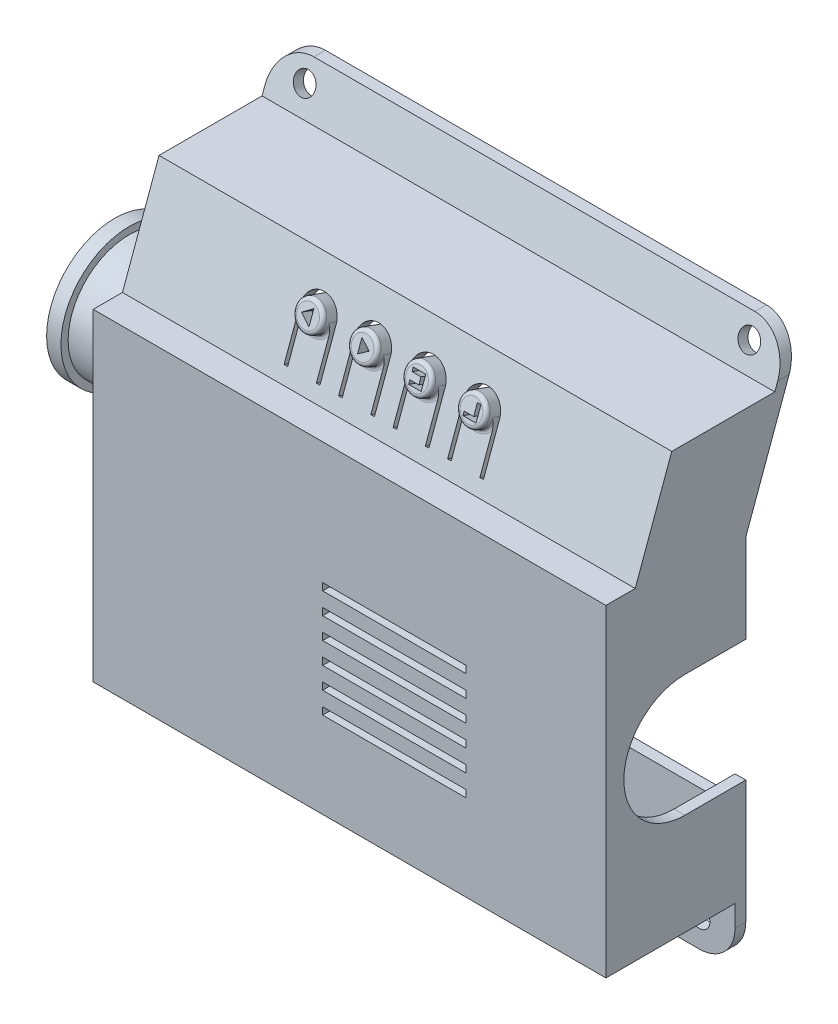
SolidWorks part; units mm, degrees
ref_plane "前视基准面" through (0, 0, 0) normal (0, 0, 1) x (1, 0, 0)
ref_plane "上视基准面" through (0, 0, 0) normal (0, 1, 0) x (1, 0, 0)
ref_plane "右视基准面" through (0, 0, 0) normal (1, 0, 0) x (0, 0, -1)
sketch "草图1" plane through (0, 0, 0) normal (0, 0, 1) x (1, 0, 0)
  line L1 (0, 0) -> (70, 0)
  line L2 (0, 0) -> (0, 42)
  line L3 (0, 42) -> (70, 42)
  line L4 (70, 0) -> (70, 42)
  dimension "D1" = 70
  dimension "D2" = 42
extrude "凸台-拉伸1" add sketch "草图1" along normal blind 1.5
sketch "草图2" plane through (0, 0, 0) normal (0, -1, 0) x (1, 0, 0)
  line L0 (70, 1.5) -> (70, 0) construction
  line L1 (0, 1.5) -> (70, 1.5)
  line L2 (0, 1.5) -> (0, -16.5)
  line L3 (0, -16.5) -> (70, -16.5)
  line L4 (70, 1.5) -> (70, -16.5)
  dimension "D1" = 18
extrude "凸台-拉伸2" add sketch "草图2" along normal blind 1.5
sketch "草图3" plane through (0, 0, -16.5) normal (0, 0, -1) x (-1, 0, 0)
  line L1 (-70, 10) -> (0, 10)
  line L2 (-70, 10) -> (-70, -9.5)
  line L3 (-70, -9.5) -> (0, -9.5)
  line L4 (0, 10) -> (0, -9.5)
  line L5 (0, -1.5) -> (-70, -1.5) construction
  line L7 (0, 0) -> (-70, 0) construction
  dimension "D1" = 8
  dimension "D2" = 10
extrude "凸台-拉伸3" add sketch "草图3" along normal blind 1.5
sketch "草图5" plane through (70, 0, 0) normal (1, 0, 0) x (0, 0, -1)
  line L0 (18, 10) -> (18, -9.5) construction
  line L1 (-1.5, 42) -> (18, 42)
  line L2 (-1.5, 42) -> (-1.5, -1.5)
  line L3 (-1.5, -1.5) -> (18, -1.5)
  line L4 (18, 42) -> (18, -1.5)
  line L5 (16.5, -1.5) -> (-1.5, -1.5) construction
extrude "凸台-拉伸4" add sketch "草图5" against normal blind 1.5
sketch "草图6" plane through (0, 0, 0) normal (-1, 0, 0) x (0, 0, 1)
  line L0 (-18, -9.5) -> (-18, 10) construction
  line L1 (1.5, 42) -> (-18, 42)
  line L2 (1.5, 42) -> (1.5, -1.5)
  line L3 (1.5, -1.5) -> (-18, -1.5)
  line L4 (-18, 42) -> (-18, -1.5)
  line L5 (1.5, -1.5) -> (-16.5, -1.5) construction
extrude "凸台-拉伸5" add sketch "草图6" along normal blind 1.5
sketch "草图7" plane through (-1.5, 0, 0) normal (-1, 0, 0) x (0, 0, 1)
  line L0 (-8, 21.5) -> (-8, 13.5) construction
  line L5 (-5, 21.5) -> (-5, 13.5)
  line L6 (-11, 21.5) -> (-11, 13.5)
  line L7 (-18, 42) -> (-18, -1.5) construction
  line L8 (-18, -1.5) -> (1.5, -1.5) construction
  arc A0 (-5, 21.5) -> (-11, 21.5) centre (-8, 21.5) ccw
  arc A1 (-11, 13.5) -> (-5, 13.5) centre (-8, 13.5) ccw
  point P2 (-8, 17.5)
  dimension "D3" = 15
  dimension "D1" = 7
  dimension "D2" = 13
  dimension "D4" = 23
extrude "切除-拉伸1" cut sketch "草图7" against normal blind 1.5
sketch "草图8" plane through (-1.5, 0, 0) normal (-1, 0, 0) x (0, 0, 1)
  line L0 (-18, 42) -> (-25.8665, 63.6129)
  line L1 (-25.8665, 63.6129) -> (-24.2702, 63.6129)
  line L2 (-24.2702, 63.6129) -> (-16.4037, 42)
  line L3 (1.5, 42) -> (-18, 42) construction
  line L4 (-18, 42) -> (-16.4037, 42)
  line L5 (-18, 42) -> (-18, -1.5) construction
  dimension "D1" = 23
  dimension "D2" = 160
  dimension "D3" = 1.5
extrude "凸台-拉伸6" add sketch "草图8" against normal blind 71.5
sketch "草图9" plane through (-1.5, 0, 0) normal (-1, 0, 0) x (0, 0, 1)
  line L0 (-3.6336, 42) -> (-8.7639, 56.0954)
  line L1 (1.5, 42) -> (-16.4037, 42) construction
  line L3 (-7.6807, 57.5049) -> (-2.5833, 43.5)
  line L5 (-16.4037, 42) -> (-24.2702, 63.6129) construction
  line L6 (-7.6807, 57.5049) -> (-22.0471, 57.5049)
  line L7 (-22.0471, 57.5049) -> (-21.534, 56.0954)
  line L8 (-21.534, 56.0954) -> (-8.7639, 56.0954)
  line L9 (-2.5833, 43.5) -> (1.5, 43.5)
  line L10 (1.5, 43.5) -> (1.5, 42)
  line L11 (1.5, 42) -> (-3.6336, 42)
  dimension "D1" = 1.5
  dimension "D2" = 12
  dimension "D3" = 1.5
  dimension "D4" = 15
extrude "凸台-拉伸7" add sketch "草图9" against normal blind 71.5
sketch "草图11" plane through (-1.5, 0, 0) normal (-1, 0, 0) x (0, 0, 1)
  line L0 (-21.534, 56.0954) -> (-8.7639, 56.0954)
  line L1 (-8.7639, 56.0954) -> (-3.6336, 42)
  line L2 (-3.6336, 42) -> (-16.4037, 42)
  line L3 (-3.6336, 42) -> (-16.4037, 42) construction
  line L4 (-16.4037, 42) -> (-21.534, 56.0954) construction
  line L5 (-16.4037, 42) -> (-21.534, 56.0954)
extrude "凸台-拉伸10" add sketch "草图11" against normal blind 1.5
sketch "草图12" plane through (70, 0, 0) normal (1, 0, 0) x (0, 0, -1)
  line L0 (8.7639, 56.0954) -> (21.534, 56.0954)
  line L1 (21.534, 56.0954) -> (16.4037, 42)
  line L2 (16.4037, 42) -> (3.6336, 42)
  line L3 (3.6336, 42) -> (8.7639, 56.0954)
extrude "凸台-拉伸11" add sketch "草图12" against normal blind 1.5
sketch "草图13" plane through (0, -0.872, -2.3959) normal (0, -0.342, -0.9397) x (-1, 0, 0)
  line L0 (0, 45.6235) -> (0, 15.5533) construction
  line L1 (-68.5, 44.6235) -> (0, 44.6235)
  line L2 (-68.5, 44.6235) -> (-68.5, 50.6235)
  line L3 (-68.5, 50.6235) -> (0, 50.6235)
  line L4 (0, 44.6235) -> (0, 50.6235)
  line L6 (-68.5, 39.4671) -> (-68.5, 0) construction
  line L7 (-68.5, 45.6235) -> (-70, 45.6235) construction
  dimension "D1" = 6
  dimension "D2" = 5
extrude "切除-拉伸2" cut sketch "草图13" against normal blind 1.5
sketch "草图14" plane through (0, 3.7453, 10.29) normal (0, -0.342, -0.9397) x (-1, 0, 0)
  line L0 (-68.5, 40.7099) -> (0, 40.7099) construction
  line L1 (-54.75, 50.6235) -> (-53.25, 50.6235)
  line L2 (-54.75, 50.6235) -> (-54.75, 55.7099)
  line L3 (-54.75, 55.7099) -> (-53.25, 55.7099)
  line L4 (-53.25, 50.6235) -> (-53.25, 55.7099)
  line L5 (-34.25, 40.7099) -> (-34.25, 65.8956) construction
  line L6 (-15.25, 50.6235) -> (-15.25, 55.7099)
  line L7 (-13.75, 55.7099) -> (-15.25, 55.7099)
  line L8 (-13.75, 50.6235) -> (-13.75, 55.7099)
  line L9 (-13.75, 50.6235) -> (-15.25, 50.6235)
  line L10 (-68.5, 55.7099) -> (0, 55.7099) construction
  line L11 (0, 50.6235) -> (-68.5, 50.6235) construction
  dimension "D1" = 1.5
  dimension "D2" = 38
extrude "凸台-拉伸12" add sketch "草图14" along normal blind 13.5
sketch "草图15" plane through (0, 4.2583, 11.6995) normal (0, 0.342, 0.9397) x (1, 0, 0)
  line L0 (34.25, 56.6639) -> (34.25, 29.0672) construction
  line L1 (70, 56.6639) -> (-1.5, 56.6639) construction
  line L2 (30.45, 51.83) -> (30.45, 31.4798) construction
  line L3 (38.05, 51.83) -> (38.05, 31.4798) construction
  line L4 (45.65, 54.4883) -> (45.65, 27.6418) construction
  line L5 (22.85, 54.4883) -> (22.85, 27.6418) construction
  line L11 (20.35, 43.7602) -> (20.35, 50.3471)
  line L17 (20.85, 43.7602) -> (20.85, 50.3471)
  line L18 (20.85, 43.7602) -> (20.35, 43.7602)
  line L19 (24.85, 43.7602) -> (25.35, 43.7602)
  line L20 (20.85, 41.7602) -> (20.85, 50.3471) construction
  line L21 (20.35, 41.7602) -> (20.35, 50.3471) construction
  line L22 (24.85, 43.7602) -> (24.85, 50.3471)
  line L23 (25.35, 43.7602) -> (25.35, 50.3471)
  line L24 (70, 41.7602) -> (-1.5, 41.7602) construction
  line L31 (26.65, 56.6639) -> (26.65, 29.0672) construction
  line L32 (27.95, 43.7602) -> (27.95, 50.3471)
  line L33 (28.45, 43.7602) -> (28.45, 50.3471)
  line L34 (28.45, 43.7602) -> (27.95, 43.7602)
  line L35 (32.45, 43.7602) -> (32.95, 43.7602)
  line L36 (32.45, 43.7602) -> (32.45, 50.3471)
  line L37 (32.95, 43.7602) -> (32.95, 50.3471)
  line L38 (35.55, 43.7602) -> (35.55, 50.3471)
  line L39 (36.05, 43.7602) -> (36.05, 50.3471)
  line L40 (36.05, 43.7602) -> (35.55, 43.7602)
  line L41 (40.05, 43.7602) -> (40.55, 43.7602)
  line L42 (40.05, 43.7602) -> (40.05, 50.3471)
  line L43 (40.55, 43.7602) -> (40.55, 50.3471)
  line L44 (43.15, 43.7602) -> (43.15, 50.3471)
  line L45 (43.65, 43.7602) -> (43.65, 50.3471)
  line L46 (43.65, 43.7602) -> (43.15, 43.7602)
  line L47 (47.65, 43.7602) -> (48.15, 43.7602)
  line L48 (47.65, 43.7602) -> (47.65, 50.3471)
  line L49 (48.15, 43.7602) -> (48.15, 50.3471)
  arc A0 (22.85, 52.8471) -> (20.35, 50.3471) centre (22.85, 50.3471) ccw
  arc A1 (22.85, 52.3471) -> (20.85, 50.3471) centre (22.85, 50.3471) ccw
  arc A2 (22.85, 52.3471) -> (24.85, 50.3471) centre (22.85, 50.3471) cw
  arc A3 (22.85, 52.8471) -> (25.35, 50.3471) centre (22.85, 50.3471) cw
  arc A8 (30.45, 52.8471) -> (27.95, 50.3471) centre (30.45, 50.3471) ccw
  arc A9 (30.45, 52.3471) -> (28.45, 50.3471) centre (30.45, 50.3471) ccw
  arc A10 (30.45, 52.3471) -> (32.45, 50.3471) centre (30.45, 50.3471) cw
  arc A11 (30.45, 52.8471) -> (32.95, 50.3471) centre (30.45, 50.3471) cw
  arc A12 (38.05, 52.8471) -> (35.55, 50.3471) centre (38.05, 50.3471) ccw
  arc A13 (38.05, 52.3471) -> (36.05, 50.3471) centre (38.05, 50.3471) ccw
  arc A14 (38.05, 52.3471) -> (40.05, 50.3471) centre (38.05, 50.3471) cw
  arc A15 (38.05, 52.8471) -> (40.55, 50.3471) centre (38.05, 50.3471) cw
  arc A16 (45.65, 52.8471) -> (43.15, 50.3471) centre (45.65, 50.3471) ccw
  arc A17 (45.65, 52.3471) -> (43.65, 50.3471) centre (45.65, 50.3471) ccw
  arc A18 (45.65, 52.3471) -> (47.65, 50.3471) centre (45.65, 50.3471) cw
  arc A19 (45.65, 52.8471) -> (48.15, 50.3471) centre (45.65, 50.3471) cw
  dimension "D1" = 7.6
  dimension "D2" = 7.6
  dimension "D4" = 4
  dimension "D5" = 2
  dimension "D3" = 0.5
extrude "切除-拉伸3" cut sketch "草图15" against normal up to next
sketch "草图16" plane through (0, 4.2583, 11.6995) normal (0, 0.342, 0.9397) x (1, 0, 0)
  line L0 (21.9503, 50.3471) -> (23.3231, 51.3556)
  line L1 (23.3231, 51.3556) -> (23.3231, 49.344)
  line L2 (23.3231, 49.344) -> (21.9503, 50.3471)
  line L3 (30.0545, 51.2434) -> (30.0545, 49.4556)
  line L4 (30.0545, 49.4556) -> (31.3755, 50.3471)
  line L5 (31.3755, 50.3471) -> (30.0545, 51.2434)
  line L6 (37.2118, 50.7504) -> (38.4609, 50.7504)
  line L7 (38.4609, 50.7504) -> (38.4609, 49.8688)
  line L8 (38.4609, 49.8688) -> (37.2118, 49.8688)
  line L9 (37.2118, 49.8688) -> (37.2118, 49.3688)
  line L10 (37.2118, 49.3688) -> (38.9609, 49.3688)
  line L11 (38.9609, 49.3688) -> (38.9609, 51.2504)
  line L12 (38.9609, 51.2504) -> (37.2118, 51.2504)
  line L13 (37.2118, 51.2504) -> (37.2118, 50.7504)
  line L14 (44.7761, 49.8688) -> (46.1088, 49.8688)
  line L15 (46.1088, 49.8688) -> (46.1088, 51.3969)
  line L16 (46.1088, 51.3969) -> (46.6088, 51.3969)
  line L17 (46.6088, 51.3969) -> (46.6088, 49.3688)
  line L18 (46.6088, 49.3688) -> (44.7761, 49.3688)
  line L19 (44.7761, 49.3688) -> (44.7761, 49.8688)
  circle A0 centre (22.85, 50.3471) radius 2
  circle A1 centre (30.45, 50.3471) radius 2
  circle A2 centre (38.05, 50.3471) radius 2
  circle A3 centre (45.65, 50.3471) radius 2
  point P32 (31.3755, 50.3471)
  point P37 (21.9503, 50.3471)
  point P38 (0, 0)
  dimension "D1" = 0.5
  dimension "D2" = 0.5
  dimension "D3" = 0.5
  dimension "D4" = 0.5
  dimension "D5" = 0.5
extrude "凸台-拉伸13" add sketch "草图16" along normal blind 1.5
fillet "圆角1" radius 0.5 8 edges at (22.85, 49.6897, -4.8361) (30.45, 49.6897, -4.8361) (38.05, 49.6897, -4.8361) (45.65, 49.6897, -4.8361) (45.65, 50.2027, -3.4266) (38.05, 50.2027, -3.4266) (30.45, 50.2027, -3.4266) (22.85, 50.2027, -3.4266)
fillet "圆角2" radius 5 4 edges at (0, -9.5, -17.25) (70, -9.5, -17.25) (70, 63.6129, -25.0683) (-1.5, 63.6129, -25.0683)
sketch "草图17" plane through (-1.5, 0, 0) normal (-1, 0, 0) x (0, 0, 1)
  line L0 (-7.6807, 57.5049) -> (-22.0471, 57.5049) construction
  line L1 (1.5, -1.5) -> (1.5, 43.5) construction
  circle A0 centre (-8.5, 36.5049) radius 7.5
  point P4 (-8.3201, 42.5049)
  dimension "D1" = 15
  dimension "D2" = 21
  dimension "D3" = 10
extrude "切除-拉伸4" cut sketch "草图17" against normal blind 2
sketch "草图18" plane through (-1.5, 0, 0) normal (-1, 0, 0) x (0, 0, 1)
  circle A0 centre (-8.5, 36.5049) radius 8.5
  circle A1 centre (-8.5, 36.5049) radius 7.5
  circle A2 centre (-8.5, 36.5049) radius 7.5 construction
  dimension "D1" = 17
extrude "凸台-拉伸14" add sketch "草图18" along normal blind 5
sketch "草图19" plane through (-6.5, 0, 0) normal (-1, 0, 0) x (0, 0, 1)
  circle A0 centre (-8.5, 36.5049) radius 7.5
  circle A1 centre (-8.5, 36.5049) radius 9.5
  circle A2 centre (-8.5, 36.5049) radius 7.5 construction
  dimension "D1" = 19
extrude "凸台-拉伸15" add sketch "草图19" along normal blind 2
sketch "草图20" plane through (70, 0, 0) normal (1, 0, 0) x (0, 0, -1)
  line L0 (9.5, 29.6554) -> (18, 29.6554)
  line L1 (18, 42) -> (18, -4.5) construction
  line L2 (18, 29.6554) -> (18, 12.6554)
  line L3 (18, 12.6554) -> (9.5, 12.6554)
  arc A0 (9.5, 29.6554) -> (9.5, 12.6554) centre (9.5, 21.1554) ccw
  point P1 (9.5, 12.4186)
  dimension "D1" = 17
  dimension "D2" = 8.5
extrude "切除-拉伸5" cut sketch "草图20" against normal blind 2
sketch "草图24" plane through (0, 0, 1.5) normal (0, 0, 1) x (1, 0, 0)
  line L0 (70, -1.5) -> (-1.5, -1.5) construction
  line L1 (30.5, 11.5) -> (50.5, 11.5)
  line L2 (30.5, 11.5) -> (30.5, 10.5)
  line L3 (30.5, 10.5) -> (50.5, 10.5)
  line L4 (50.5, 11.5) -> (50.5, 10.5)
  line L5 (-1.5, -1.5) -> (-1.5, 43.5) construction
  line L6 (30.5, 14.5) -> (50.5, 14.5)
  line L7 (30.5, 14.5) -> (30.5, 13.5)
  line L8 (30.5, 13.5) -> (50.5, 13.5)
  line L9 (50.5, 14.5) -> (50.5, 13.5)
  line L10 (30.5, 17.5) -> (50.5, 17.5)
  line L11 (30.5, 17.5) -> (30.5, 16.5)
  line L12 (30.5, 16.5) -> (50.5, 16.5)
  line L13 (50.5, 17.5) -> (50.5, 16.5)
  line L14 (30.5, 20.5) -> (50.5, 20.5)
  line L15 (30.5, 20.5) -> (30.5, 19.5)
  line L16 (30.5, 19.5) -> (50.5, 19.5)
  line L17 (50.5, 20.5) -> (50.5, 19.5)
  line L18 (30.5, 23.5) -> (50.5, 23.5)
  line L19 (30.5, 23.5) -> (30.5, 22.5)
  line L20 (30.5, 22.5) -> (50.5, 22.5)
  line L21 (50.5, 23.5) -> (50.5, 22.5)
  line L22 (30.5, 26.5) -> (50.5, 26.5)
  line L23 (30.5, 26.5) -> (30.5, 25.5)
  line L24 (30.5, 25.5) -> (50.5, 25.5)
  line L25 (50.5, 26.5) -> (50.5, 25.5)
  dimension "D1" = 20
  dimension "D2" = 1
  dimension "D3" = 12
  dimension "D4" = 32
  dimension "D5" = 6
extrude "切除-拉伸6" cut sketch "草图24" against normal blind 2
sketch "草图25" plane through (0, 0, -16.5) normal (0, 0, 1) x (1, 0, 0)
  line L0 (35, -9.5) -> (35, -16.6904) construction
  line L1 (65, -9.5) -> (5, -9.5) construction
  line L2 (0, -1.5) -> (70, -1.5) construction
  circle A0 centre (5, -5.5) radius 1.5
  circle A1 centre (65, -5.5) radius 1.5
  dimension "D1" = 3
  dimension "D2" = 60
  dimension "D3" = 4
extrude "切除-拉伸7" cut sketch "草图25" against normal blind 2
sketch "草图26" plane through (0, -0.359, -0.9863) normal (0, 0.342, 0.9397) x (1, 0, 0)
  line L0 (34.25, 68.0775) -> (34.25, 62.9127) construction
  line L1 (65, 68.0775) -> (3.5, 68.0775) construction
  line L2 (70, 61.5775) -> (-1.5, 61.5775) construction
  circle A0 centre (3.25, 65.0775) radius 1.5
  circle A1 centre (65.25, 65.0775) radius 1.5
  dimension "D1" = 3
  dimension "D2" = 62
  dimension "D3" = 3.5
extrude "切除-拉伸8" cut sketch "草图26" against normal blind 2
